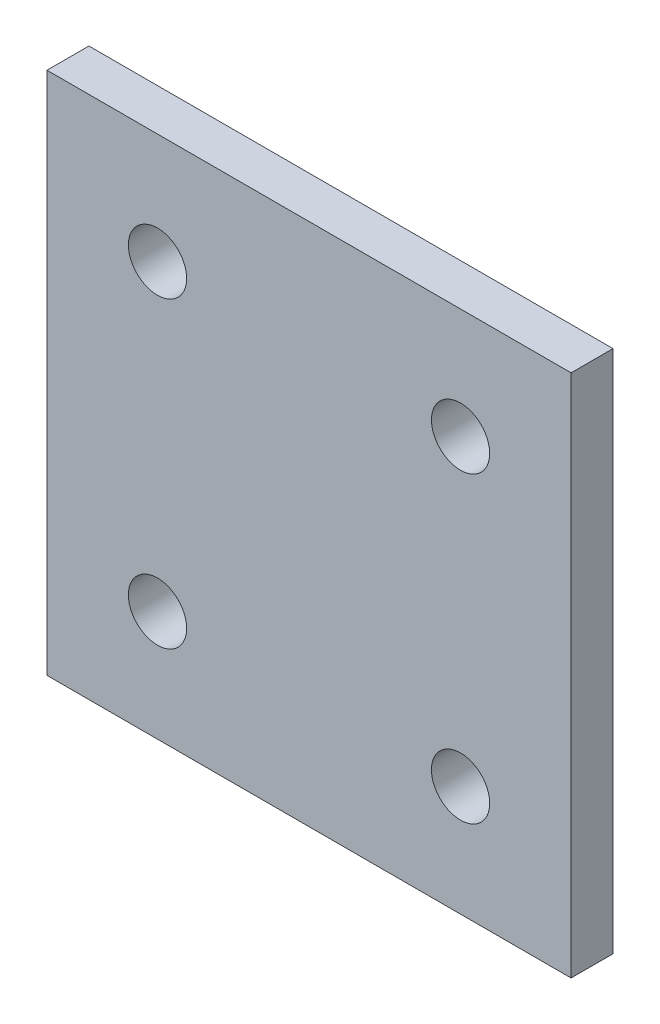
SolidWorks part; units mm, degrees
ref_plane "Front Plane" through (0, 0, 0) normal (0, 0, 1) x (1, 0, 0)
ref_plane "Top Plane" through (0, 0, 0) normal (0, 1, 0) x (1, 0, 0)
ref_plane "Right Plane" through (0, 0, 0) normal (1, 0, 0) x (0, 0, -1)
sketch "Sketch1" plane through (0, 0, 0) normal (0, 0, 1) x (1, 0, 0)
  line L5 (-28.575, -28.575) -> (28.575, -28.575)
  line L6 (-28.575, -28.575) -> (-28.575, 28.575)
  line L7 (-28.575, 28.575) -> (28.575, 28.575)
  line L8 (28.575, -28.575) -> (28.575, 28.575)
  line L9 (-28.575, -28.575) -> (28.575, 28.575) construction
  line L10 (-28.575, 28.575) -> (28.575, -28.575) construction
  circle A0 centre (-16.5221, 16.5221) radius 3.175
  circle A1 centre (16.5221, 16.5221) radius 3.175
  circle A2 centre (16.5221, -16.5221) radius 3.175
  circle A3 centre (-16.5221, -16.5221) radius 3.175
  circle A4 centre (0, 0) radius 11.3
  point P0 (0, 0)
  point P1 (0, 0)
  point P20 (0, 0)
  dimension "D3" = 22.6
  dimension "D4" = 6.35
  dimension "D1" = 57.15
  dimension "D2" = 4
extrude "Boss-Extrude1" add sketch "Sketch1" along normal blind 2.032
extrude "Boss-Extrude2" add sketch "Sketch1<2>" along normal blind 2.54 from surface contours A4 | L5 L8 L7 L6 A4 A3 A2 A1 A0 region at (-27.7668, 0, 0) region at (0, 0, 0) starting at face at (0, 0, 2.032)
sketch "Sketch1<2>" plane through (0, 0, 0) normal (0, 0, 1) x (1, 0, 0) same geometry as "Sketch1"
equation "\"bolt\"=0.25"
equation "\"D4@Sketch1\"=\"bolt\""
